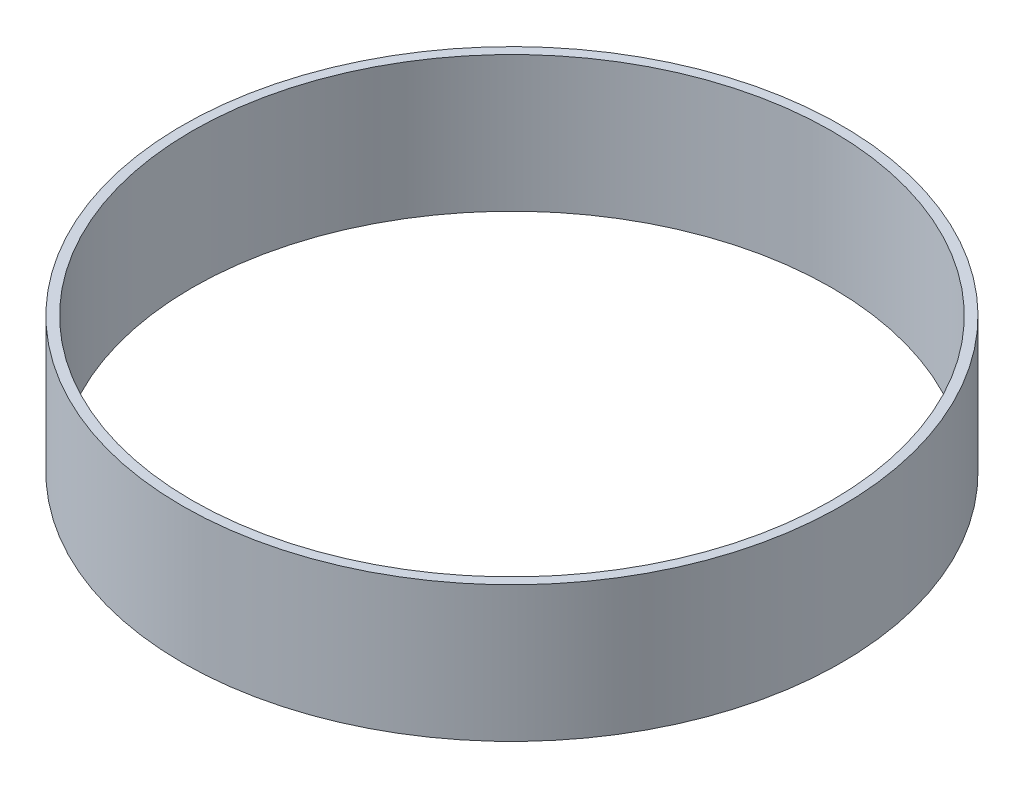
SolidWorks part; units mm, degrees
ref_plane "Front Plane" through (0, 0, 0) normal (0, 0, 1) x (1, 0, 0)
ref_plane "Top Plane" through (0, 0, 0) normal (0, 1, 0) x (1, 0, 0)
ref_plane "Right Plane" through (0, 0, 0) normal (1, 0, 0) x (0, 0, -1)
ref_axis "Axis1" through (0, 0, 0) along (0, 1, 0)
sketch "Sketch1" plane through (0, 0, 0) normal (0, 0, 1) x (1, 0, 0)
  line L0 (0, 0) -> (0, -9746.6064) construction
  line L12 (-33, -7) -> (-33, 7)
  line L13 (-33, 7) -> (-34, 7)
  line L14 (-34, 7) -> (-34, -7)
  line L20 (-34, -7) -> (-33, -7)
  point P5 (-33, 0)
  dimension "D1" = 14
  dimension "D2" = 68
  dimension "D3" = 66
revolve "Revolve1" add sketch "Sketch1" angle 360 about L0
